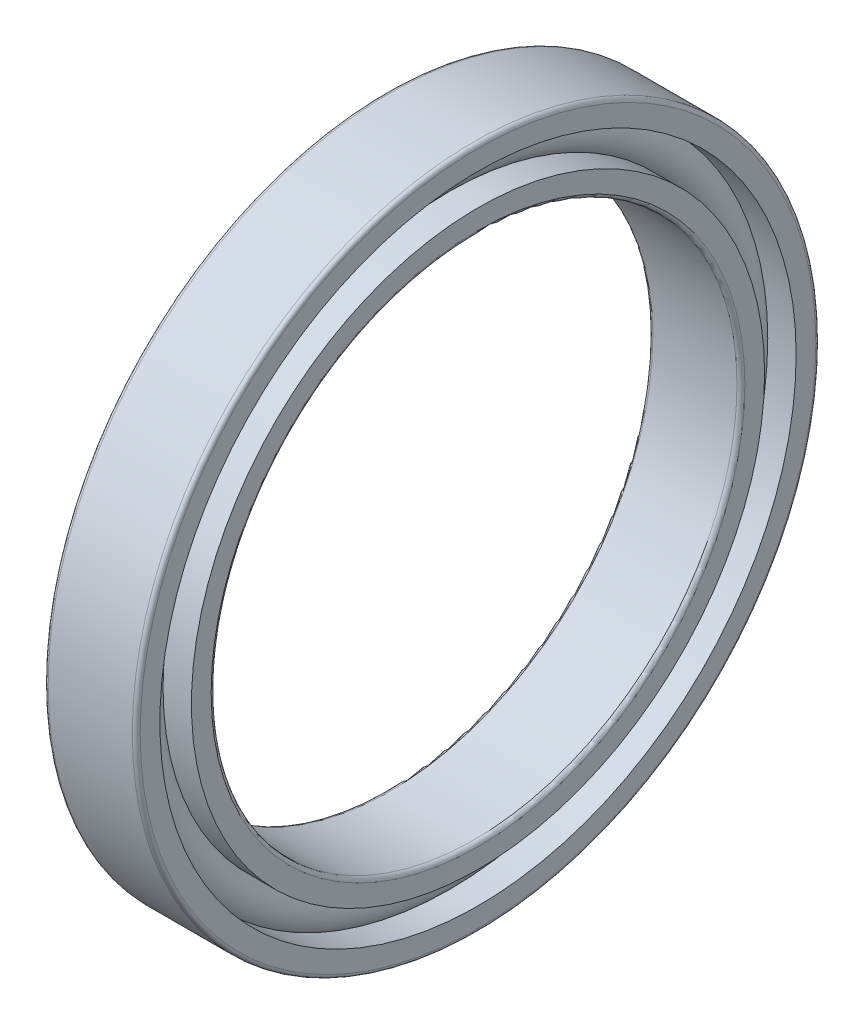
SolidWorks part; units mm, degrees
ref_plane "Plane1" through (0, 0, 0) normal (0, 0, 1) x (1, 0, 0)
ref_plane "Plane2" through (0, 0, 0) normal (0, 1, 0) x (1, 0, 0)
ref_plane "Plane3" through (0, 0, 0) normal (1, 0, 0) x (0, 0, -1)
sketch "Clipboard" plane through (0, 0, 0) normal (0, 0, 1) x (1, 0, 0)
  line L0 (-10, 0) -> (10, 0) construction
  line L1 (0, 0) -> (22.3471, -0.7804)
  line L2 (0, 0) -> (22.986, 0.8027)
  line L3 (0, 0) -> (22.3471, -0.7804)
  line L4 (0, 0) -> (-22.3573, -0.3902)
  dimension "BallCLRad" = 23
sketch "CagSpiSke" plane through (0, 0, 0) normal (0, 0, 1) x (1, 0, 0)
  line L0 (0.18, 22.7) -> (0.18, 23.3)
  line L1 (0.18, 23.3) -> (-0.18, 23.3)
  line L2 (-0.18, 23.3) -> (-0.18, 22.7)
  line L3 (-0.18, 22.7) -> (0.18, 22.7)
  line L4 (-20.6375, 0) -> (20.6375, 0) construction
  line L5 (0, 0) -> (0, 23.7692) construction
  dimension "OD" = 46.6
  dimension "ID" = 45.4
revolve "CageSpine" add sketch "CagSpiSke" angle 0.001 about L4 reverse direction yes
ref_axis "Axis1" through (-50, 0, 0) along (1, 0, 0)
sketch "CagBalSke" plane through (0, 0, 0) normal (0, 0, 1) x (1, 0, 0)
  line L0 (-1.98, 23) -> (1.98, 23)
  line L1 (-1.905, 23) -> (1.905, 23) construction
  line L2 (-10, 0) -> (10, 0) construction
  line L3 (0, 0) -> (0, 24) construction
  arc A0 (1.98, 23) -> (-1.98, 23) centre (0, 23) cw
  dimension "BallCLRad" = 23
revolve "CageBall" [suppressed] add sketch "CagBalSke" angle 360 about L1 reverse direction yes
pattern_circular "CageBalls" [suppressed] count 2 every 180 about axis through (-50, 0, 0) along (1, 0, 0)
sketch "CagTrmODSke" plane through (0, 0, 0) normal (0, 0, 1) x (1, 0, 0)
  line L0 (1.981, 23.3) -> (1.981, 24.981)
  line L1 (1.981, 24.981) -> (-1.981, 24.981)
  line L2 (-1.981, 24.981) -> (-1.981, 23.3)
  line L3 (-1.981, 23.3) -> (1.981, 23.3)
  line L4 (-20.6375, 0) -> (20.6375, 0) construction
  line L5 (0, 0) -> (0, 25) construction
  dimension "Width" = 3.962
  dimension "ID" = 46.6
  dimension "OD" = 49.962
revolve "CageTrimOD" [suppressed] cut sketch "CagTrmODSke" angle 360 about L4 reverse direction yes
sketch "CagTrmIDSke" plane through (0, 0, 0) normal (0, 0, 1) x (1, 0, 0)
  line L0 (1.981, 21.021) -> (1.981, 22.7)
  line L1 (1.981, 22.7) -> (-1.981, 22.7)
  line L2 (-1.981, 22.7) -> (-1.981, 21.021)
  line L3 (-1.981, 21.021) -> (1.981, 21.021)
  line L4 (-20.6375, 0) -> (20.6375, 0) construction
  line L5 (0, 0) -> (0, 25) construction
  dimension "Width" = 3.962
  dimension "ID" = 42.042
  dimension "OD" = 45.4
revolve "CageTrimID" [suppressed] cut sketch "CagTrmIDSke" angle 360 about L4 reverse direction yes
sketch "BalSimSke" plane through (0, 0, 0) normal (0, 0, 1) x (1, 0, 0)
  line L0 (-10, 0) -> (10, 0) construction
  line L1 (-10, 23) -> (10, 23) construction
  line L2 (0, 0) -> (0, 23) construction
  circle A0 centre (0, 23) radius 1.8
  dimension "BallCLRad" = 23
  dimension "Ball_diameter" = 3.6
revolve "BallsSimplified" add sketch "BalSimSke" angle 360 about L0
sketch "BalDetSke" plane through (0, 0, 0) normal (0, 0, 1) x (1, 0, 0)
  line L0 (-1.8, 23) -> (1.8, 23)
  line L1 (-1.905, 23) -> (1.905, 23) construction
  line L2 (0, 0) -> (0, 25) construction
  arc A0 (1.8, 23) -> (-1.8, 23) centre (0, 23) cw
  dimension "BallCLRad" = 23
  dimension "Ball_diameter" = 3.6
revolve "BallDetailed" [suppressed] add sketch "BalDetSke" angle 360 about L1 reverse direction yes
sketch "InnRacSke" plane through (0, 0, 0) normal (0, 0, 1) x (1, 0, 0)
  line L0 (-1.3079, 21.8) -> (-3.5, 21.8)
  line L1 (-3.5, 21.8) -> (-3.5, 20.3)
  line L2 (-3.2, 20) -> (3.2, 20)
  line L3 (3.5, 20.3) -> (3.5, 21.8)
  line L4 (3.5, 21.8) -> (1.3079, 21.8)
  line L5 (-20.6375, 0) -> (20.6375, 0) construction
  line L6 (0, 0) -> (0, 30) construction
  arc A0 (-3.5, 20.3) -> (-3.2, 20) centre (-3.2, 20.3) ccw
  arc A1 (3.2, 20) -> (3.5, 20.3) centre (3.2, 20.3) ccw
  arc A2 (1.3079, 21.8) -> (-1.3079, 21.8) centre (0, 23) cw
  dimension "BallCLRad" = 23
  dimension "Fillet_radius" = 0.3
  dimension "Ball_diameter" = 3.55
  dimension "ID" = 40
  dimension "OD" = 43.6
  dimension "Width" = 7
revolve "InnerRace" add sketch "InnRacSke" angle 360 about L5 reverse direction yes
sketch "OutRacSke" plane through (0, 0, 0) normal (0, 0, 1) x (1, 0, 0)
  line L0 (-1.3079, 24.2) -> (-3.5, 24.2)
  line L1 (-3.5, 24.2) -> (-3.5, 25.7)
  line L2 (-3.2, 26) -> (3.2, 26)
  line L3 (3.5, 25.7) -> (3.5, 24.2)
  line L4 (3.5, 24.2) -> (1.3079, 24.2)
  line L5 (-20.6375, 0) -> (20.6375, 0) construction
  line L6 (0, 0) -> (0, 30) construction
  arc A0 (-3.5, 25.7) -> (-3.2, 26) centre (-3.2, 25.7) cw
  arc A1 (3.2, 26) -> (3.5, 25.7) centre (3.2, 25.7) cw
  arc A2 (1.3079, 24.2) -> (-1.3079, 24.2) centre (0, 23) ccw
  dimension "BallCLRad" = 23
  dimension "Fillet_radius" = 0.3
  dimension "Ball_diameter" = 3.55
  dimension "Width" = 7
revolve "OuterRace" add sketch "OutRacSke" angle 360 about L5 reverse direction yes
pattern_circular "BallsDetailed" [suppressed] count 2 every 180 about axis through (-50, 0, 0) along (1, 0, 0)
equation "\"BallCLRad@Clipboard\" = ( \"OD@OutRacSke\" + \"ID@InnRacSke\" ) / 4"
equation "\"BallCLRad@BalSimSke\" = \"BallCLRad@Clipboard\""
equation "\"BallCLRad@BalDetSke\" = \"BallCLRad@Clipboard\""
equation "\"BallCLRad@InnRacSke\" = \"BallCLRad@Clipboard\""
equation "\"BallCLRad@OutRacSke\" = \"BallCLRad@Clipboard\""
equation "\"Ball_diameter@InnRacSke\" = \"Ball_diameter@BalDetSke\" - 0.05"
equation "\"Ball_diameter@OutRacSke\" = \"Ball_diameter@BalDetSke\" - 0.05"
equation "\"Ball_diameter@BalSimSke\" = \"Ball_diameter@BalDetSke\""
equation "\"Width@OutRacSke\" = \"Width@InnRacSke\""
equation "\"Fillet_radius@OutRacSke\" = \"Fillet_radius@InnRacSke\""
equation "\"Max_count@Clipboard\" = int( 3.14159265 / atn(( \"Ball_diameter@BalDetSke\" / 2) / sqr( \"BallCLRad@Clipboard\"  *  \"BallCLRad@Clipboard\" - ( \"Ball_diameter@BalDetSke\" / 2) *  ( \"Ball_diameter@BalDetSke\" / 2))))"
equation "\"Max_count@Clipboard\" = ((sgn( \"Max_count@Clipboard\" - \"Count@Clipboard\" )-1)*( \"Max_count@Clipboard\" - \"Count@Clipboard\" ))/-2+ \"Count@Clipboard\""
equation "\"Count@BallsDetailed\" = int( \"Show_count@Clipboard\" ) "
equation "\"Count@BallsDetailed\" = ((sgn( \"Count@BallsDetailed\" - \"Max_count@Clipboard\" )-1)*( \"Count@BallsDetailed\" - \"Max_count@Clipboard\" ))/-2+ \"Max_count@Clipboard\""
equation "\"Count@BallsDetailed\" = ((sgn( \"Count@BallsDetailed\" - \"Min_count@Clipboard\" )+1)*( \"Count@BallsDetailed\" - \"Min_count@Clipboard\"))/2 +\"Min_count@Clipboard\""
equation "\"Angle@BallsDetailed\" = 360.0 / \"Max_count@Clipboard\""
equation "\"BallCLRad@CagBalSke\" = \"BallCLRad@Clipboard\""
equation "\"Count@CageBalls\" = \"Count@BallsDetailed\""
equation "\"Angle@CageBalls\" = \"Angle@BallsDetailed\""
equation "\"Angle@CageSpine\" =  \"Angle@CageBalls\" * ( \"Count@CageBalls\" -1 + int( \"Count@CageBalls\" / \"Max_count@Clipboard\" ) )  + 0.001 -  int( \"Count@CageBalls\" / \"Max_count@Clipboard\" ) * 0.001"
equation "\"Angle@CageSpine\" =  \"Angle@CageSpine\" * int( \"Min_count@Clipboard\" / 2) + int(1 / \"Min_count@Clipboard\")  * 0.001"
equation "\"CageWallOD@CagBalSke\" =  \"Ball_diameter@BalDetSke\" * 1.1"
equation "\"Thickness@CagSpiSke\" =  \"Ball_diameter@BalDetSke\" * 0.1"
equation "\"OD@CagTrmODSke\" = \"BallCLRad@Clipboard\" * 2 + \"CageWallOD@CagBalSke\" + 0.002"
equation "\"ID@CagTrmODSke\" = \"BallCLRad@Clipboard\" * 2 + \"Ball_diameter@BalDetSke\" / 6"
equation "\"OD@CagTrmIDSke\" = \"BallCLRad@Clipboard\" * 2 - \"Ball_diameter@BalDetSke\" / 6"
equation "\"ID@CagTrmIDSke\" = \"BallCLRad@Clipboard\" * 2 - \"CageWallOD@CagBalSke\" + 0.002"
equation "\"OD@CagSpiSke\" = \"ID@CagTrmODSke\""
equation "\"ID@CagSpiSke\" = \"OD@CagTrmIDSke\""
equation "\"Width@CagTrmODSke\" = \"CageWallOD@CagBalSke\" + 0.002"
equation "\"Width@CagTrmIDSke\" = \"CageWallOD@CagBalSke\" + 0.002"
